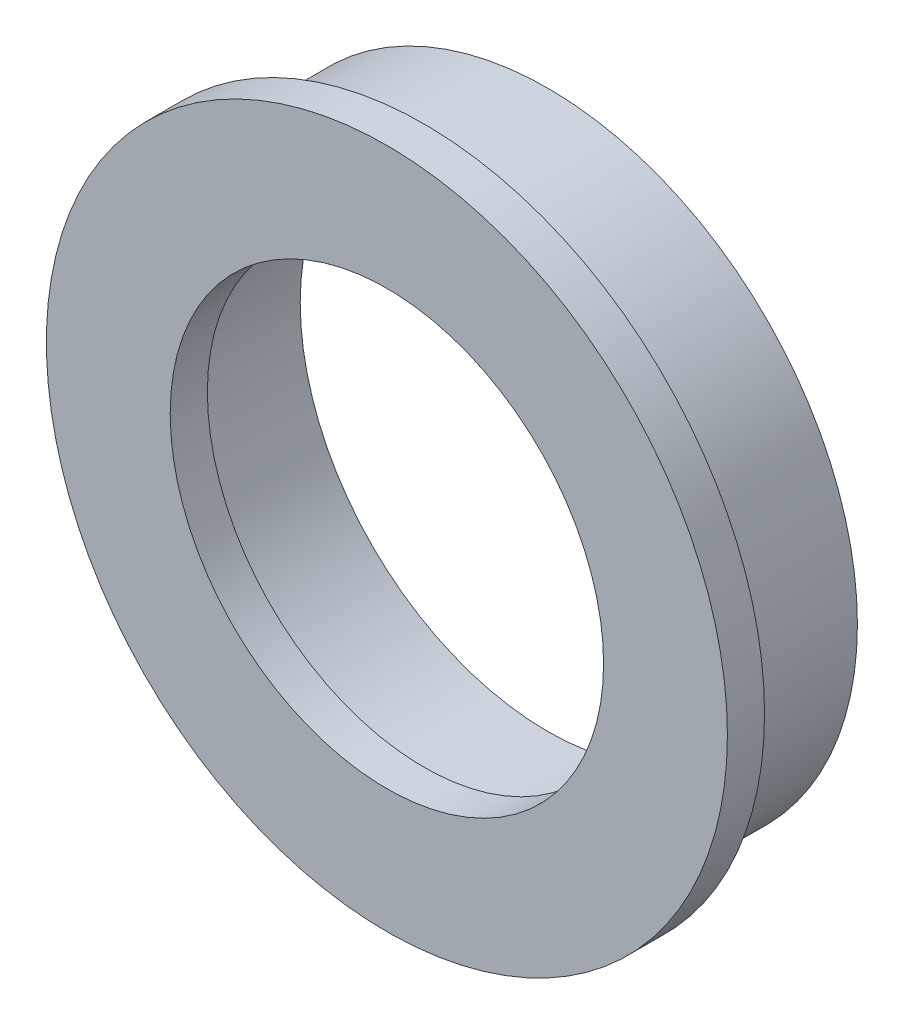
SolidWorks part; units mm, degrees
ref_plane "Спереди" through (0, 0, 0) normal (0, 0, 1) x (1, 0, 0)
ref_plane "Сверху" through (0, 0, 0) normal (0, 1, 0) x (1, 0, 0)
ref_plane "Справа" through (0, 0, 0) normal (1, 0, 0) x (0, 0, -1)
sketch "Эскиз1" plane through (0, 0, 0) normal (0, 0, 1) x (1, 0, 0)
  circle A0 centre (0, 0) radius 25
  dimension "D1" = 50
extrude "Бобышка-Вытянуть2" add sketch "Эскиз1" along normal blind 10
sketch "Эскиз2" plane through (0, 0, 0) normal (0, 0, 1) x (1, 0, 0)
  circle A0 centre (0, 0) radius 27.5
  dimension "D1" = 55
extrude "Бобышка-Вытянуть3" add sketch "Эскиз2" along normal blind 3 from offset 10
sketch "Эскиз3" plane through (0, 0, 0) normal (0, 0, 1) x (1, 0, 0)
  circle A0 centre (0, 0) radius 20
  dimension "D1" = 40
extrude "Вырез-Вытянуть1" cut sketch "Эскиз3" along normal blind 10
sketch "Эскиз4" plane through (0, 0, 0) normal (0, 0, 1) x (1, 0, 0)
  circle A0 centre (0, 0) radius 17.5
  dimension "D1" = 35
extrude "Вырез-Вытянуть2" cut sketch "Эскиз4" along normal blind 13
sketch "Эскиз5" plane through (0, 0, 10) normal (0, 0, -1) x (-1, 0, 0)
  line L2 (0, 0) -> (27.5, 0)
  line L3 (0, 0) -> (27.3954, -2.3968)
  line L4 (0, 0) -> (27.0822, -4.7753)
  line L5 (0, 0) -> (26.563, -7.1175)
  line L6 (0, 0) -> (25.8415, -9.4056)
  line L7 (0, 0) -> (24.9235, -11.622)
  line L8 (0, 0) -> (23.8157, -13.75)
  line L9 (0, 0) -> (22.5267, -15.7734)
  line L10 (0, 0) -> (21.0662, -17.6767)
  line L11 (0, 0) -> (19.4454, -19.4454)
  line L12 (0, 0) -> (17.6767, -21.0662)
  line L13 (0, 0) -> (15.7734, -22.5267)
  line L14 (0, 0) -> (13.75, -23.8157)
  line L15 (0, 0) -> (11.622, -24.9235)
  line L16 (0, 0) -> (9.4056, -25.8415)
  line L17 (0, 0) -> (7.1175, -26.563)
  line L18 (0, 0) -> (4.7753, -27.0822)
  line L19 (0, 0) -> (2.3968, -27.3954)
  line L20 (0, 0) -> (0, -27.5)
  line L21 (0, 0) -> (-2.3968, -27.3954)
  line L22 (0, 0) -> (-4.7753, -27.0822)
  line L23 (0, 0) -> (-7.1175, -26.563)
  line L24 (0, 0) -> (-9.4056, -25.8415)
  line L25 (0, 0) -> (-11.622, -24.9235)
  line L26 (0, 0) -> (-13.75, -23.8157)
  line L27 (0, 0) -> (-15.7734, -22.5267)
  line L28 (0, 0) -> (-17.6767, -21.0662)
  line L29 (0, 0) -> (-19.4454, -19.4454)
  line L30 (0, 0) -> (-21.0662, -17.6767)
  line L31 (0, 0) -> (-22.5267, -15.7734)
  line L32 (0, 0) -> (-23.8157, -13.75)
  line L33 (0, 0) -> (-24.9235, -11.622)
  line L34 (0, 0) -> (-25.8415, -9.4056)
  line L35 (0, 0) -> (-26.563, -7.1175)
  line L36 (0, 0) -> (-27.0822, -4.7753)
  line L37 (0, 0) -> (-27.3954, -2.3968)
  line L38 (0, 0) -> (-27.5, 0)
  line L39 (0, 0) -> (-27.3954, 2.3968)
  line L40 (0, 0) -> (-27.0822, 4.7753)
  line L41 (0, 0) -> (-26.563, 7.1175)
  line L42 (0, 0) -> (-25.8415, 9.4056)
  line L43 (0, 0) -> (-24.9235, 11.622)
  line L44 (0, 0) -> (-23.8157, 13.75)
  line L45 (0, 0) -> (-22.5267, 15.7734)
  line L46 (0, 0) -> (-21.0662, 17.6767)
  line L47 (0, 0) -> (-19.4454, 19.4454)
  line L48 (0, 0) -> (-17.6767, 21.0662)
  line L49 (0, 0) -> (-15.7734, 22.5267)
  line L50 (0, 0) -> (-13.75, 23.8157)
  line L51 (0, 0) -> (-11.622, 24.9235)
  line L52 (0, 0) -> (-9.4056, 25.8415)
  line L53 (0, 0) -> (-7.1175, 26.563)
  line L54 (0, 0) -> (-4.7753, 27.0822)
  line L55 (0, 0) -> (-2.3968, 27.3954)
  line L56 (0, 0) -> (0, 27.5)
  line L57 (0, 0) -> (2.3968, 27.3954)
  line L58 (0, 0) -> (4.7753, 27.0822)
  line L59 (0, 0) -> (7.1175, 26.563)
  line L60 (0, 0) -> (9.4056, 25.8415)
  line L61 (0, 0) -> (11.622, 24.9235)
  line L62 (0, 0) -> (13.75, 23.8157)
  line L63 (0, 0) -> (15.7734, 22.5267)
  line L64 (0, 0) -> (17.6767, 21.0662)
  line L65 (0, 0) -> (19.4454, 19.4454)
  line L66 (0, 0) -> (21.0662, 17.6767)
  line L67 (0, 0) -> (22.5267, 15.7734)
  line L68 (0, 0) -> (23.8157, 13.75)
  line L69 (0, 0) -> (24.9235, 11.622)
  line L70 (0, 0) -> (25.8415, 9.4056)
  line L71 (0, 0) -> (26.563, 7.1175)
  line L72 (0, 0) -> (27.0822, 4.7753)
  line L73 (0, 0) -> (27.3954, 2.3968)
  circle A1 centre (0, 0) radius 27.5 construction
  circle A2 centre (0, 0) radius 27.5
  circle A3 centre (0, 0) radius 17.5
  point P7 (0, 0)
  point P80 (0, 0)
  dimension "D1" = 72
  dimension "D2" = 35
  dimension "D3" = 55
sketch "Эскиз6" plane through (0, 0, 13) normal (0, 0, 1) x (1, 0, 0)
  line L0 (0, 0) -> (-27.5, 0)
  line L1 (0, 0) -> (-27.3954, 2.3968)
  line L2 (0, 0) -> (-27.0822, 4.7753)
  line L3 (0, 0) -> (-26.563, 7.1175)
  line L4 (0, 0) -> (-25.8415, 9.4056)
  line L5 (0, 0) -> (-24.9235, 11.622)
  line L6 (0, 0) -> (-23.8157, 13.75)
  line L7 (0, 0) -> (-22.5267, 15.7734)
  line L8 (0, 0) -> (-21.0662, 17.6767)
  line L9 (0, 0) -> (-19.4454, 19.4454)
  line L10 (0, 0) -> (-17.6767, 21.0662)
  line L11 (0, 0) -> (-15.7734, 22.5267)
  line L12 (0, 0) -> (-13.75, 23.8157)
  line L13 (0, 0) -> (-11.622, 24.9235)
  line L14 (0, 0) -> (-9.4056, 25.8415)
  line L15 (0, 0) -> (-7.1175, 26.563)
  line L16 (0, 0) -> (-4.7753, 27.0822)
  line L17 (0, 0) -> (-2.3968, 27.3954)
  line L18 (0, 0) -> (0, 27.5)
  line L19 (0, 0) -> (2.3968, 27.3954)
  line L20 (0, 0) -> (4.7753, 27.0822)
  line L21 (0, 0) -> (7.1175, 26.563)
  line L22 (0, 0) -> (9.4056, 25.8415)
  line L23 (0, 0) -> (11.622, 24.9235)
  line L24 (0, 0) -> (13.75, 23.8157)
  line L25 (0, 0) -> (15.7734, 22.5267)
  line L26 (0, 0) -> (17.6767, 21.0662)
  line L27 (0, 0) -> (19.4454, 19.4454)
  line L28 (0, 0) -> (21.0662, 17.6767)
  line L29 (0, 0) -> (22.5267, 15.7734)
  line L30 (0, 0) -> (23.8157, 13.75)
  line L31 (0, 0) -> (24.9235, 11.622)
  line L32 (0, 0) -> (25.8415, 9.4056)
  line L33 (0, 0) -> (26.563, 7.1175)
  line L34 (0, 0) -> (27.0822, 4.7753)
  line L35 (0, 0) -> (27.3954, 2.3968)
  line L36 (0, 0) -> (27.5, 0)
  line L37 (0, 0) -> (27.3954, -2.3968)
  line L38 (0, 0) -> (27.0822, -4.7753)
  line L39 (0, 0) -> (26.563, -7.1175)
  line L40 (0, 0) -> (25.8415, -9.4056)
  line L41 (0, 0) -> (24.9235, -11.622)
  line L42 (0, 0) -> (23.8157, -13.75)
  line L43 (0, 0) -> (22.5267, -15.7734)
  line L44 (0, 0) -> (21.0662, -17.6767)
  line L45 (0, 0) -> (19.4454, -19.4454)
  line L46 (0, 0) -> (17.6767, -21.0662)
  line L47 (0, 0) -> (15.7734, -22.5267)
  line L48 (0, 0) -> (13.75, -23.8157)
  line L49 (0, 0) -> (11.622, -24.9235)
  line L50 (0, 0) -> (9.4056, -25.8415)
  line L51 (0, 0) -> (7.1175, -26.563)
  line L52 (0, 0) -> (4.7753, -27.0822)
  line L53 (0, 0) -> (2.3968, -27.3954)
  line L54 (0, 0) -> (0, -27.5)
  line L55 (0, 0) -> (-2.3968, -27.3954)
  line L56 (0, 0) -> (-4.7753, -27.0822)
  line L57 (0, 0) -> (-7.1175, -26.563)
  line L58 (0, 0) -> (-9.4056, -25.8415)
  line L59 (0, 0) -> (-11.622, -24.9235)
  line L60 (0, 0) -> (-13.75, -23.8157)
  line L61 (0, 0) -> (-15.7734, -22.5267)
  line L62 (0, 0) -> (-17.6767, -21.0662)
  line L63 (0, 0) -> (-19.4454, -19.4454)
  line L64 (0, 0) -> (-21.0662, -17.6767)
  line L65 (0, 0) -> (-22.5267, -15.7734)
  line L66 (0, 0) -> (-23.8157, -13.75)
  line L67 (0, 0) -> (-24.9235, -11.622)
  line L68 (0, 0) -> (-25.8415, -9.4056)
  line L69 (0, 0) -> (-26.563, -7.1175)
  line L70 (0, 0) -> (-27.0822, -4.7753)
  line L71 (0, 0) -> (-27.3954, -2.3968)
  circle A0 centre (0, 0) radius 27.5
  circle A1 centre (0, 0) radius 17.5
  point P78 (0, 0)
  dimension "D2" = 35
  dimension "D3" = 55
  dimension "D1" = 72
sketch3d "Трехмерный эскиз2"
  line L4 (27.3954, 2.3968, 13) -> (17.4334, 1.5252, 13)
  line L5 (17.4334, 1.5252, 13) -> (17.5, 0, 10)
  line L6 (27.5, 0, 10) -> (17.5, 0, 10)
  line L7 (27.3954, 2.3968, 13) -> (27.5, 0, 10)
  line L8 (0, 0, 13) -> (0, 0, -49987) construction
  circle A0 centre (0, 0, 13) radius 17.5 construction
  circle A1 centre (0, 0, 10) radius 17.5 construction
  point P11 (0, 0, 30.5)
  point P15 (0, 0, -7.5)
sketch3d "Трехмерный эскиз3"
  line L0 (27.5, 0, 13) -> (17.5, 0, 13)
  line L1 (0, 0, 13) -> (27.5, 0, 13) construction
  line L2 (17.5, 0, 13) -> (17.4334, -1.5252, 10)
  line L3 (0, 0, 10) -> (27.3954, -2.3968, 10) construction
  line L4 (17.4334, -1.5252, 10) -> (27.3954, -2.3968, 10)
  line L5 (27.3954, -2.3968, 10) -> (27.5, 0, 13)
  line L6 (27.3954, -2.3968, 13) -> (27.0822, -4.7753, 10)
  line L7 (27.0822, -4.7753, 10) -> (17.2341, -3.0388, 10)
  line L8 (0, 0, 10) -> (27.0822, -4.7753, 10) construction
  line L9 (17.2341, -3.0388, 10) -> (17.4334, -1.5252, 13)
  line L10 (0, 0, 13) -> (27.3954, -2.3968, 13) construction
  line L11 (27.3954, -2.3968, 13) -> (17.4334, -1.5252, 13)
  line L12 (26.563, -7.1175, 10) -> (27.0822, -4.7753, 13)
  line L13 (27.0822, -4.7753, 13) -> (17.2341, -3.0388, 13)
  line L14 (0, 0, 13) -> (27.0822, -4.7753, 13) construction
  line L15 (17.2341, -3.0388, 13) -> (16.9037, -4.5293, 10)
  line L16 (0, 0, 10) -> (26.563, -7.1175, 10) construction
  line L17 (16.9037, -4.5293, 10) -> (26.563, -7.1175, 10)
  line L18 (26.563, -7.1175, 13) -> (25.8415, -9.4056, 10)
  line L19 (25.8415, -9.4056, 10) -> (16.4446, -5.9854, 10)
  line L20 (0, 0, 10) -> (25.8415, -9.4056, 10) construction
  line L21 (16.4446, -5.9854, 10) -> (16.9037, -4.5293, 13)
  line L22 (0, 0, 13) -> (26.563, -7.1175, 13) construction
  line L23 (16.9037, -4.5293, 13) -> (26.563, -7.1175, 13)
  line L24 (24.9235, -11.622, 10) -> (25.8415, -9.4056, 13)
  line L25 (25.8415, -9.4056, 13) -> (16.4446, -5.9854, 13)
  line L26 (0, 0, 13) -> (25.8415, -9.4056, 13) construction
  line L27 (16.4446, -5.9854, 13) -> (15.8604, -7.3958, 10)
  line L28 (0, 0, 10) -> (24.9235, -11.622, 10) construction
  line L29 (15.8604, -7.3958, 10) -> (24.9235, -11.622, 10)
  line L30 (23.8157, -13.75, 10) -> (24.9235, -11.622, 13)
  line L31 (24.9235, -11.622, 13) -> (15.8604, -7.3958, 13)
  line L32 (0, 0, 13) -> (24.9235, -11.622, 13) construction
  line L33 (15.8604, -7.3958, 13) -> (15.1554, -8.75, 10)
  line L34 (0, 0, 10) -> (23.8157, -13.75, 10) construction
  line L35 (15.1554, -8.75, 10) -> (23.8157, -13.75, 10)
  line L36 (22.5267, -15.7734, 10) -> (23.8157, -13.75, 13)
  line L37 (23.8157, -13.75, 13) -> (15.1554, -8.75, 13)
  line L38 (0, 0, 13) -> (23.8157, -13.75, 13) construction
  line L39 (15.1554, -8.75, 13) -> (14.3352, -10.0376, 10)
  line L40 (0, 0, 10) -> (22.5267, -15.7734, 10) construction
  line L41 (14.3352, -10.0376, 10) -> (22.5267, -15.7734, 10)
  line L42 (22.5267, -15.7734, 13) -> (14.3352, -10.0376, 13)
  line L43 (0, 0, 13) -> (22.5267, -15.7734, 13) construction
  line L44 (22.5267, -15.7734, 13) -> (21.0662, -17.6767, 10)
  line L45 (21.0662, -17.6767, 10) -> (13.4058, -11.2488, 10)
  line L46 (0, 0, 10) -> (21.0662, -17.6767, 10) construction
  line L47 (13.4058, -11.2488, 10) -> (14.3352, -10.0376, 13)
  line L48 (21.0662, -17.6767, 13) -> (19.4454, -19.4454, 10)
  line L49 (21.0662, -17.6767, 13) -> (13.4058, -11.2488, 13)
  line L50 (0, 0, 13) -> (21.0662, -17.6767, 13) construction
  line L51 (13.4058, -11.2488, 13) -> (12.3744, -12.3744, 10)
  line L52 (0, 0, 10) -> (19.4454, -19.4454, 10) construction
  line L53 (12.3744, -12.3744, 10) -> (19.4454, -19.4454, 10)
  line L54 (19.4454, -19.4454, 13) -> (17.6767, -21.0662, 10)
  line L55 (17.6767, -21.0662, 10) -> (11.2488, -13.4058, 10)
  line L56 (0, 0, 10) -> (17.6767, -21.0662, 10) construction
  line L57 (11.2488, -13.4058, 10) -> (12.3744, -12.3744, 13)
  line L58 (0, 0, 13) -> (19.4454, -19.4454, 13) construction
  line L59 (12.3744, -12.3744, 13) -> (19.4454, -19.4454, 13)
  line L60 (17.6767, -21.0662, 13) -> (15.7734, -22.5267, 10)
  line L61 (15.7734, -22.5267, 10) -> (10.0376, -14.3352, 10)
  line L62 (0, 0, 10) -> (15.7734, -22.5267, 10) construction
  line L63 (10.0376, -14.3352, 10) -> (11.2488, -13.4058, 13)
  line L64 (0, 0, 13) -> (17.6767, -21.0662, 13) construction
  line L65 (11.2488, -13.4058, 13) -> (17.6767, -21.0662, 13)
  line L66 (13.75, -23.8157, 10) -> (15.7734, -22.5267, 13)
  line L67 (15.7734, -22.5267, 13) -> (10.0376, -14.3352, 13)
  line L68 (0, 0, 13) -> (15.7734, -22.5267, 13) construction
  line L69 (10.0376, -14.3352, 13) -> (8.75, -15.1554, 10)
  line L70 (0, 0, 10) -> (13.75, -23.8157, 10) construction
  line L71 (8.75, -15.1554, 10) -> (13.75, -23.8157, 10)
  line L72 (11.622, -24.9235, 10) -> (13.75, -23.8157, 13)
  line L73 (13.75, -23.8157, 13) -> (8.75, -15.1554, 13)
  line L74 (0, 0, 13) -> (13.75, -23.8157, 13) construction
  line L75 (8.75, -15.1554, 13) -> (7.3958, -15.8604, 10)
  line L76 (0, 0, 10) -> (11.622, -24.9235, 10) construction
  line L77 (7.3958, -15.8604, 10) -> (11.622, -24.9235, 10)
  line L78 (9.4056, -25.8415, 10) -> (11.622, -24.9235, 13)
  line L79 (11.622, -24.9235, 13) -> (7.3958, -15.8604, 13)
  line L80 (0, 0, 13) -> (11.622, -24.9235, 13) construction
  line L81 (7.3958, -15.8604, 13) -> (5.9854, -16.4446, 10)
  line L82 (0, 0, 10) -> (9.4056, -25.8415, 10) construction
  line L83 (5.9854, -16.4446, 10) -> (9.4056, -25.8415, 10)
  line L84 (7.1175, -26.563, 10) -> (9.4056, -25.8415, 13)
  line L85 (9.4056, -25.8415, 13) -> (5.9854, -16.4446, 13)
  line L86 (0, 0, 13) -> (9.4056, -25.8415, 13) construction
  line L87 (5.9854, -16.4446, 13) -> (4.5293, -16.9037, 10)
  line L88 (0, 0, 10) -> (7.1175, -26.563, 10) construction
  line L89 (4.5293, -16.9037, 10) -> (7.1175, -26.563, 10)
  line L90 (4.7753, -27.0822, 10) -> (7.1175, -26.563, 13)
  line L91 (7.1175, -26.563, 13) -> (4.5293, -16.9037, 13)
  line L92 (0, 0, 13) -> (7.1175, -26.563, 13) construction
  line L93 (4.5293, -16.9037, 13) -> (3.0388, -17.2341, 10)
  line L94 (0, 0, 10) -> (4.7753, -27.0822, 10) construction
  line L95 (3.0388, -17.2341, 10) -> (4.7753, -27.0822, 10)
  line L96 (2.3968, -27.3954, 10) -> (4.7753, -27.0822, 13)
  line L97 (4.7753, -27.0822, 13) -> (3.0388, -17.2341, 13)
  line L98 (0, 0, 13) -> (4.7753, -27.0822, 13) construction
  line L99 (3.0388, -17.2341, 13) -> (1.5252, -17.4334, 10)
  line L100 (0, 0, 10) -> (2.3968, -27.3954, 10) construction
  line L101 (1.5252, -17.4334, 10) -> (2.3968, -27.3954, 10)
  line L102 (2.3968, -27.3954, 13) -> (1.5252, -17.4334, 13)
  line L103 (0, 0, 13) -> (2.3968, -27.3954, 13) construction
  line L104 (1.5252, -17.4334, 13) -> (0, -17.5, 10)
  line L105 (0, 0, 10) -> (0, -27.5, 10) construction
  line L106 (0, -17.5, 10) -> (0, -27.5, 10)
  line L107 (0, -27.5, 10) -> (2.3968, -27.3954, 13)
  line L108 (-2.3968, -27.3954, 10) -> (0, -27.5, 13)
  line L109 (0, -27.5, 13) -> (0, -17.5, 13)
  line L110 (0, 0, 13) -> (0, -27.5, 13) construction
  line L111 (0, -17.5, 13) -> (-1.5252, -17.4334, 10)
  line L112 (0, 0, 10) -> (-2.3968, -27.3954, 10) construction
  line L113 (-1.5252, -17.4334, 10) -> (-2.3968, -27.3954, 10)
  line L114 (-4.7753, -27.0822, 10) -> (-2.3968, -27.3954, 13)
  line L115 (-2.3968, -27.3954, 13) -> (-1.5252, -17.4334, 13)
  line L116 (0, 0, 13) -> (-2.3968, -27.3954, 13) construction
  line L117 (-1.5252, -17.4334, 13) -> (-3.0388, -17.2341, 10)
  line L118 (0, 0, 10) -> (-4.7753, -27.0822, 10) construction
  line L119 (-3.0388, -17.2341, 10) -> (-4.7753, -27.0822, 10)
  line L120 (-7.1175, -26.563, 10) -> (-4.7753, -27.0822, 13)
  line L121 (-4.7753, -27.0822, 13) -> (-3.0388, -17.2341, 13)
  line L122 (0, 0, 13) -> (-4.7753, -27.0822, 13) construction
  line L123 (-3.0388, -17.2341, 13) -> (-4.5293, -16.9037, 10)
  line L124 (0, 0, 10) -> (-7.1175, -26.563, 10) construction
  line L125 (-4.5293, -16.9037, 10) -> (-7.1175, -26.563, 10)
  line L126 (-9.4056, -25.8415, 10) -> (-7.1175, -26.563, 13)
  line L127 (-7.1175, -26.563, 13) -> (-4.5293, -16.9037, 13)
  line L128 (0, 0, 13) -> (-7.1175, -26.563, 13) construction
  line L129 (-4.5293, -16.9037, 13) -> (-5.9854, -16.4446, 10)
  line L130 (0, 0, 10) -> (-9.4056, -25.8415, 10) construction
  line L131 (-5.9854, -16.4446, 10) -> (-9.4056, -25.8415, 10)
  line L132 (-11.622, -24.9235, 10) -> (-9.4056, -25.8415, 13)
  line L133 (-9.4056, -25.8415, 13) -> (-5.9854, -16.4446, 13)
  line L134 (0, 0, 13) -> (-9.4056, -25.8415, 13) construction
  line L135 (-5.9854, -16.4446, 13) -> (-7.3958, -15.8604, 10)
  line L136 (0, 0, 10) -> (-11.622, -24.9235, 10) construction
  line L137 (-7.3958, -15.8604, 10) -> (-11.622, -24.9235, 10)
  line L138 (-13.75, -23.8157, 10) -> (-11.622, -24.9235, 13)
  line L139 (-11.622, -24.9235, 13) -> (-7.3958, -15.8604, 13)
  line L140 (0, 0, 13) -> (-11.622, -24.9235, 13) construction
  line L141 (-7.3958, -15.8604, 13) -> (-8.75, -15.1554, 10)
  line L142 (0, 0, 10) -> (-13.75, -23.8157, 10) construction
  line L143 (-8.75, -15.1554, 10) -> (-13.75, -23.8157, 10)
  line L144 (-15.7734, -22.5267, 10) -> (-13.75, -23.8157, 13)
  line L145 (-13.75, -23.8157, 13) -> (-8.75, -15.1554, 13)
  line L146 (0, 0, 13) -> (-13.75, -23.8157, 13) construction
  line L147 (-8.75, -15.1554, 13) -> (-10.0376, -14.3352, 10)
  line L148 (0, 0, 10) -> (-15.7734, -22.5267, 10) construction
  line L149 (-10.0376, -14.3352, 10) -> (-15.7734, -22.5267, 10)
  line L150 (-17.6767, -21.0662, 10) -> (-15.7734, -22.5267, 13)
  line L151 (-15.7734, -22.5267, 13) -> (-10.0376, -14.3352, 13)
  line L152 (0, 0, 13) -> (-15.7734, -22.5267, 13) construction
  line L153 (-10.0376, -14.3352, 13) -> (-11.2488, -13.4058, 10)
  line L154 (0, 0, 10) -> (-17.6767, -21.0662, 10) construction
  line L155 (-11.2488, -13.4058, 10) -> (-17.6767, -21.0662, 10)
  line L156 (-19.4454, -19.4454, 10) -> (-17.6767, -21.0662, 13)
  line L157 (-17.6767, -21.0662, 13) -> (-11.2488, -13.4058, 13)
  line L158 (0, 0, 13) -> (-17.6767, -21.0662, 13) construction
  line L159 (-11.2488, -13.4058, 13) -> (-12.3744, -12.3744, 10)
  line L160 (0, 0, 10) -> (-19.4454, -19.4454, 10) construction
  line L161 (-12.3744, -12.3744, 10) -> (-19.4454, -19.4454, 10)
  line L162 (-21.0662, -17.6767, 10) -> (-19.4454, -19.4454, 13)
  line L163 (-19.4454, -19.4454, 13) -> (-12.3744, -12.3744, 13)
  line L164 (0, 0, 13) -> (-19.4454, -19.4454, 13) construction
  line L165 (-12.3744, -12.3744, 13) -> (-13.4058, -11.2488, 10)
  line L166 (0, 0, 10) -> (-21.0662, -17.6767, 10) construction
  line L167 (-13.4058, -11.2488, 10) -> (-21.0662, -17.6767, 10)
  line L168 (-22.5267, -15.7734, 10) -> (-21.0662, -17.6767, 13)
  line L169 (-21.0662, -17.6767, 13) -> (-13.4058, -11.2488, 13)
  line L170 (0, 0, 13) -> (-21.0662, -17.6767, 13) construction
  line L171 (-13.4058, -11.2488, 13) -> (-14.3352, -10.0376, 10)
  line L172 (0, 0, 10) -> (-22.5267, -15.7734, 10) construction
  line L173 (-14.3352, -10.0376, 10) -> (-22.5267, -15.7734, 10)
  line L174 (-23.8157, -13.75, 10) -> (-22.5267, -15.7734, 13)
  line L175 (-22.5267, -15.7734, 13) -> (-14.3352, -10.0376, 13)
  line L176 (0, 0, 13) -> (-22.5267, -15.7734, 13) construction
  line L177 (-14.3352, -10.0376, 13) -> (-15.1554, -8.75, 10)
  line L178 (0, 0, 10) -> (-23.8157, -13.75, 10) construction
  line L179 (-15.1554, -8.75, 10) -> (-23.8157, -13.75, 10)
  line L180 (-24.9235, -11.622, 10) -> (-23.8157, -13.75, 13)
  line L181 (-23.8157, -13.75, 13) -> (-15.1554, -8.75, 13)
  line L182 (0, 0, 13) -> (-23.8157, -13.75, 13) construction
  line L183 (-15.1554, -8.75, 13) -> (-15.8604, -7.3958, 10)
  line L184 (0, 0, 10) -> (-24.9235, -11.622, 10) construction
  line L185 (-15.8604, -7.3958, 10) -> (-24.9235, -11.622, 10)
  line L186 (-25.8415, -9.4056, 10) -> (-24.9235, -11.622, 13)
  line L187 (-24.9235, -11.622, 13) -> (-15.8604, -7.3958, 13)
  line L188 (0, 0, 13) -> (-24.9235, -11.622, 13) construction
  line L189 (-15.8604, -7.3958, 13) -> (-16.4446, -5.9854, 10)
  line L190 (0, 0, 10) -> (-25.8415, -9.4056, 10) construction
  line L191 (-16.4446, -5.9854, 10) -> (-25.8415, -9.4056, 10)
  line L192 (-26.563, -7.1175, 10) -> (-25.8415, -9.4056, 13)
  line L193 (-25.8415, -9.4056, 13) -> (-16.4446, -5.9854, 13)
  line L194 (0, 0, 13) -> (-25.8415, -9.4056, 13) construction
  line L195 (-16.4446, -5.9854, 13) -> (-16.9037, -4.5293, 10)
  line L196 (0, 0, 10) -> (-26.563, -7.1175, 10) construction
  line L197 (-16.9037, -4.5293, 10) -> (-26.563, -7.1175, 10)
  line L198 (-27.0822, -4.7753, 10) -> (-26.563, -7.1175, 13)
  line L199 (-26.563, -7.1175, 13) -> (-16.9037, -4.5293, 13)
  line L200 (0, 0, 13) -> (-26.563, -7.1175, 13) construction
  line L201 (-16.9037, -4.5293, 13) -> (-17.2341, -3.0388, 10)
  line L202 (0, 0, 10) -> (-27.0822, -4.7753, 10) construction
  line L203 (-17.2341, -3.0388, 10) -> (-27.0822, -4.7753, 10)
  line L204 (-27.3954, -2.3968, 10) -> (-27.0822, -4.7753, 13)
  line L205 (-27.0822, -4.7753, 13) -> (-17.2341, -3.0388, 13)
  line L206 (0, 0, 13) -> (-27.0822, -4.7753, 13) construction
  line L207 (-17.2341, -3.0388, 13) -> (-17.4334, -1.5252, 10)
  line L208 (0, 0, 10) -> (-27.3954, -2.3968, 10) construction
  line L209 (-17.4334, -1.5252, 10) -> (-27.3954, -2.3968, 10)
  line L210 (-27.5, 0, 10) -> (-27.3954, -2.3968, 13)
  line L211 (-27.3954, -2.3968, 13) -> (-17.4334, -1.5252, 13)
  line L212 (0, 0, 13) -> (-27.3954, -2.3968, 13) construction
  line L213 (-17.4334, -1.5252, 13) -> (-17.5, 0, 10)
  line L214 (0, 0, 10) -> (-27.5, 0, 10) construction
  line L215 (-17.5, 0, 10) -> (-27.5, 0, 10)
  line L216 (-27.3954, 2.3968, 10) -> (-27.5, 0, 13)
  line L217 (-27.5, 0, 13) -> (-17.5, 0, 13)
  line L218 (0, 0, 13) -> (-27.5, 0, 13) construction
  line L219 (-17.5, 0, 13) -> (-17.4334, 1.5252, 10)
  line L220 (0, 0, 10) -> (-27.3954, 2.3968, 10) construction
  line L221 (-17.4334, 1.5252, 10) -> (-27.3954, 2.3968, 10)
  line L222 (-27.0822, 4.7753, 10) -> (-27.3954, 2.3968, 13)
  line L223 (-27.3954, 2.3968, 13) -> (-17.4334, 1.5252, 13)
  line L224 (0, 0, 13) -> (-27.3954, 2.3968, 13) construction
  line L225 (-17.4334, 1.5252, 13) -> (-17.2341, 3.0388, 10)
  line L226 (0, 0, 10) -> (-27.0822, 4.7753, 10) construction
  line L227 (-17.2341, 3.0388, 10) -> (-27.0822, 4.7753, 10)
  line L228 (-26.563, 7.1175, 10) -> (-27.0822, 4.7753, 13)
  line L229 (-27.0822, 4.7753, 13) -> (-17.2341, 3.0388, 13)
  line L230 (0, 0, 13) -> (-27.0822, 4.7753, 13) construction
  line L231 (-17.2341, 3.0388, 13) -> (-16.9037, 4.5293, 10)
  line L232 (0, 0, 10) -> (-26.563, 7.1175, 10) construction
  line L233 (-16.9037, 4.5293, 10) -> (-26.563, 7.1175, 10)
  line L234 (-25.8415, 9.4056, 10) -> (-26.563, 7.1175, 13)
  line L235 (-26.563, 7.1175, 13) -> (-16.9037, 4.5293, 13)
  line L236 (0, 0, 13) -> (-26.563, 7.1175, 13) construction
  line L237 (-16.9037, 4.5293, 13) -> (-16.4446, 5.9854, 10)
  line L238 (0, 0, 10) -> (-25.8415, 9.4056, 10) construction
  line L239 (-16.4446, 5.9854, 10) -> (-25.8415, 9.4056, 10)
  line L240 (-24.9235, 11.622, 10) -> (-25.8415, 9.4056, 13)
  line L241 (-25.8415, 9.4056, 13) -> (-16.4446, 5.9854, 13)
  line L242 (0, 0, 13) -> (-25.8415, 9.4056, 13) construction
  line L243 (-16.4446, 5.9854, 13) -> (-15.8604, 7.3958, 10)
  line L244 (0, 0, 10) -> (-24.9235, 11.622, 10) construction
  line L245 (-15.8604, 7.3958, 10) -> (-24.9235, 11.622, 10)
  line L246 (-23.8157, 13.75, 10) -> (-24.9235, 11.622, 13)
  line L247 (-24.9235, 11.622, 13) -> (-15.8604, 7.3958, 13)
  line L248 (0, 0, 13) -> (-24.9235, 11.622, 13) construction
  line L249 (-15.8604, 7.3958, 13) -> (-15.1554, 8.75, 10)
  line L250 (0, 0, 10) -> (-23.8157, 13.75, 10) construction
  line L251 (-15.1554, 8.75, 10) -> (-23.8157, 13.75, 10)
  line L252 (-22.5267, 15.7734, 10) -> (-23.8157, 13.75, 13)
  line L253 (-23.8157, 13.75, 13) -> (-15.1554, 8.75, 13)
  line L254 (0, 0, 13) -> (-23.8157, 13.75, 13) construction
  line L255 (-15.1554, 8.75, 13) -> (-14.3352, 10.0376, 10)
  line L256 (0, 0, 10) -> (-22.5267, 15.7734, 10) construction
  line L257 (-14.3352, 10.0376, 10) -> (-22.5267, 15.7734, 10)
  line L258 (-21.0662, 17.6767, 10) -> (-22.5267, 15.7734, 13)
  line L259 (-22.5267, 15.7734, 13) -> (-14.3352, 10.0376, 13)
  line L260 (0, 0, 13) -> (-22.5267, 15.7734, 13) construction
  line L261 (-14.3352, 10.0376, 13) -> (-13.4058, 11.2488, 10)
  line L262 (0, 0, 10) -> (-21.0662, 17.6767, 10) construction
  line L263 (-13.4058, 11.2488, 10) -> (-21.0662, 17.6767, 10)
  line L264 (-19.4454, 19.4454, 10) -> (-21.0662, 17.6767, 13)
  line L265 (-21.0662, 17.6767, 13) -> (-13.4058, 11.2488, 13)
  line L266 (0, 0, 13) -> (-21.0662, 17.6767, 13) construction
  line L267 (-13.4058, 11.2488, 13) -> (-12.3744, 12.3744, 10)
  line L268 (0, 0, 10) -> (-19.4454, 19.4454, 10) construction
  line L269 (-12.3744, 12.3744, 10) -> (-19.4454, 19.4454, 10)
  line L270 (-17.6767, 21.0662, 10) -> (-19.4454, 19.4454, 13)
  line L271 (-19.4454, 19.4454, 13) -> (-12.3744, 12.3744, 13)
  line L272 (0, 0, 13) -> (-19.4454, 19.4454, 13) construction
  line L273 (-12.3744, 12.3744, 13) -> (-11.2488, 13.4058, 10)
  line L274 (0, 0, 10) -> (-17.6767, 21.0662, 10) construction
  line L275 (-11.2488, 13.4058, 10) -> (-17.6767, 21.0662, 10)
  line L276 (-15.7734, 22.5267, 10) -> (-17.6767, 21.0662, 13)
  line L277 (-17.6767, 21.0662, 13) -> (-11.2488, 13.4058, 13)
  line L278 (0, 0, 13) -> (-17.6767, 21.0662, 13) construction
  line L279 (-11.2488, 13.4058, 13) -> (-10.0376, 14.3352, 10)
  line L280 (0, 0, 10) -> (-15.7734, 22.5267, 10) construction
  line L281 (-10.0376, 14.3352, 10) -> (-15.7734, 22.5267, 10)
  line L282 (-13.75, 23.8157, 10) -> (-15.7734, 22.5267, 13)
  line L283 (-15.7734, 22.5267, 13) -> (-10.0376, 14.3352, 13)
  line L284 (0, 0, 13) -> (-15.7734, 22.5267, 13) construction
  line L285 (-10.0376, 14.3352, 13) -> (-8.75, 15.1554, 10)
  line L286 (0, 0, 10) -> (-13.75, 23.8157, 10) construction
  line L287 (-8.75, 15.1554, 10) -> (-13.75, 23.8157, 10)
  line L288 (-11.622, 24.9235, 10) -> (-13.75, 23.8157, 13)
  line L289 (-13.75, 23.8157, 13) -> (-8.75, 15.1554, 13)
  line L290 (0, 0, 13) -> (-13.75, 23.8157, 13) construction
  line L291 (-8.75, 15.1554, 13) -> (-7.3958, 15.8604, 10)
  line L292 (0, 0, 10) -> (-11.622, 24.9235, 10) construction
  line L293 (-7.3958, 15.8604, 10) -> (-11.622, 24.9235, 10)
  line L294 (-9.4056, 25.8415, 10) -> (-11.622, 24.9235, 13)
  line L295 (-11.622, 24.9235, 13) -> (-7.3958, 15.8604, 13)
  line L296 (0, 0, 13) -> (-11.622, 24.9235, 13) construction
  line L297 (-7.3958, 15.8604, 13) -> (-5.9854, 16.4446, 10)
  line L298 (0, 0, 10) -> (-9.4056, 25.8415, 10) construction
  line L299 (-5.9854, 16.4446, 10) -> (-9.4056, 25.8415, 10)
  line L300 (-7.1175, 26.563, 10) -> (-9.4056, 25.8415, 13)
  line L301 (-9.4056, 25.8415, 13) -> (-5.9854, 16.4446, 13)
  line L302 (0, 0, 13) -> (-9.4056, 25.8415, 13) construction
  line L303 (-5.9854, 16.4446, 13) -> (-4.5293, 16.9037, 10)
  line L304 (0, 0, 10) -> (-7.1175, 26.563, 10) construction
  line L305 (-4.5293, 16.9037, 10) -> (-7.1175, 26.563, 10)
  line L306 (-4.7753, 27.0822, 10) -> (-7.1175, 26.563, 13)
  line L307 (-7.1175, 26.563, 13) -> (-4.5293, 16.9037, 13)
  line L308 (0, 0, 13) -> (-7.1175, 26.563, 13) construction
  line L309 (-4.5293, 16.9037, 13) -> (-3.0388, 17.2341, 10)
  line L310 (0, 0, 10) -> (-4.7753, 27.0822, 10) construction
  line L311 (-3.0388, 17.2341, 10) -> (-4.7753, 27.0822, 10)
  line L312 (-2.3968, 27.3954, 10) -> (-4.7753, 27.0822, 13)
  line L313 (-4.7753, 27.0822, 13) -> (-3.0388, 17.2341, 13)
  line L314 (0, 0, 13) -> (-4.7753, 27.0822, 13) construction
  line L315 (-3.0388, 17.2341, 13) -> (-1.5252, 17.4334, 10)
  line L316 (0, 0, 10) -> (-2.3968, 27.3954, 10) construction
  line L317 (-1.5252, 17.4334, 10) -> (-2.3968, 27.3954, 10)
  line L318 (0, 27.5, 10) -> (-2.3968, 27.3954, 13)
  line L319 (-2.3968, 27.3954, 13) -> (-1.5252, 17.4334, 13)
  line L320 (0, 0, 13) -> (-2.3968, 27.3954, 13) construction
  line L321 (-1.5252, 17.4334, 13) -> (0, 17.5, 10)
  line L322 (0, 0, 10) -> (0, 27.5, 10) construction
  line L323 (0, 17.5, 10) -> (0, 27.5, 10)
  line L324 (2.3968, 27.3954, 10) -> (0, 27.5, 13)
  line L325 (0, 27.5, 13) -> (0, 17.5, 13)
  line L326 (0, 0, 13) -> (0, 27.5, 13) construction
  line L327 (0, 17.5, 13) -> (1.5252, 17.4334, 10)
  line L328 (0, 0, 10) -> (2.3968, 27.3954, 10) construction
  line L329 (1.5252, 17.4334, 10) -> (2.3968, 27.3954, 10)
  line L330 (4.7753, 27.0822, 10) -> (2.3968, 27.3954, 13)
  line L331 (2.3968, 27.3954, 13) -> (1.5252, 17.4334, 13)
  line L332 (0, 0, 13) -> (2.3968, 27.3954, 13) construction
  line L333 (1.5252, 17.4334, 13) -> (3.0388, 17.2341, 10)
  line L334 (0, 0, 10) -> (4.7753, 27.0822, 10) construction
  line L335 (3.0388, 17.2341, 10) -> (4.7753, 27.0822, 10)
  line L336 (7.1175, 26.563, 10) -> (4.7753, 27.0822, 13)
  line L337 (4.7753, 27.0822, 13) -> (3.0388, 17.2341, 13)
  line L338 (0, 0, 13) -> (4.7753, 27.0822, 13) construction
  line L339 (3.0388, 17.2341, 13) -> (4.5293, 16.9037, 10)
  line L340 (0, 0, 10) -> (7.1175, 26.563, 10) construction
  line L341 (4.5293, 16.9037, 10) -> (7.1175, 26.563, 10)
  line L342 (9.4056, 25.8415, 10) -> (7.1175, 26.563, 13)
  line L343 (7.1175, 26.563, 13) -> (4.5293, 16.9037, 13)
  line L344 (0, 0, 13) -> (7.1175, 26.563, 13) construction
  line L345 (4.5293, 16.9037, 13) -> (5.9854, 16.4446, 10)
  line L346 (0, 0, 10) -> (9.4056, 25.8415, 10) construction
  line L347 (5.9854, 16.4446, 10) -> (9.4056, 25.8415, 10)
  line L348 (11.622, 24.9235, 10) -> (9.4056, 25.8415, 13)
  line L349 (9.4056, 25.8415, 13) -> (5.9854, 16.4446, 13)
  line L350 (0, 0, 13) -> (9.4056, 25.8415, 13) construction
  line L351 (5.9854, 16.4446, 13) -> (7.3958, 15.8604, 10)
  line L352 (0, 0, 10) -> (11.622, 24.9235, 10) construction
  line L353 (7.3958, 15.8604, 10) -> (11.622, 24.9235, 10)
  line L354 (13.75, 23.8157, 10) -> (11.622, 24.9235, 13)
  line L355 (11.622, 24.9235, 13) -> (7.3958, 15.8604, 13)
  line L356 (0, 0, 13) -> (11.622, 24.9235, 13) construction
  line L357 (7.3958, 15.8604, 13) -> (8.75, 15.1554, 10)
  line L358 (0, 0, 10) -> (13.75, 23.8157, 10) construction
  line L359 (8.75, 15.1554, 10) -> (13.75, 23.8157, 10)
  line L360 (15.7734, 22.5267, 10) -> (13.75, 23.8157, 13)
  line L361 (13.75, 23.8157, 13) -> (8.75, 15.1554, 13)
  line L362 (0, 0, 13) -> (13.75, 23.8157, 13) construction
  line L363 (8.75, 15.1554, 13) -> (10.0376, 14.3352, 10)
  line L364 (0, 0, 10) -> (15.7734, 22.5267, 10) construction
  line L365 (10.0376, 14.3352, 10) -> (15.7734, 22.5267, 10)
  line L366 (17.6767, 21.0662, 10) -> (15.7734, 22.5267, 13)
  line L367 (15.7734, 22.5267, 13) -> (10.0376, 14.3352, 13)
  line L368 (0, 0, 13) -> (15.7734, 22.5267, 13) construction
  line L369 (10.0376, 14.3352, 13) -> (11.2488, 13.4058, 10)
  line L370 (0, 0, 10) -> (17.6767, 21.0662, 10) construction
  line L371 (11.2488, 13.4058, 10) -> (17.6767, 21.0662, 10)
  line L372 (19.4454, 19.4454, 10) -> (17.6767, 21.0662, 13)
  line L373 (17.6767, 21.0662, 13) -> (11.2488, 13.4058, 13)
  line L374 (0, 0, 13) -> (17.6767, 21.0662, 13) construction
  line L375 (11.2488, 13.4058, 13) -> (12.3744, 12.3744, 10)
  line L376 (0, 0, 10) -> (19.4454, 19.4454, 10) construction
  line L377 (12.3744, 12.3744, 10) -> (19.4454, 19.4454, 10)
  line L378 (21.0662, 17.6767, 10) -> (19.4454, 19.4454, 13)
  line L379 (19.4454, 19.4454, 13) -> (12.3744, 12.3744, 13)
  line L380 (0, 0, 13) -> (19.4454, 19.4454, 13) construction
  line L381 (12.3744, 12.3744, 13) -> (13.4058, 11.2488, 10)
  line L382 (0, 0, 10) -> (21.0662, 17.6767, 10) construction
  line L383 (13.4058, 11.2488, 10) -> (21.0662, 17.6767, 10)
  line L384 (22.5267, 15.7734, 10) -> (21.0662, 17.6767, 13)
  line L385 (21.0662, 17.6767, 13) -> (13.4058, 11.2488, 13)
  line L386 (0, 0, 13) -> (21.0662, 17.6767, 13) construction
  line L387 (13.4058, 11.2488, 13) -> (14.3352, 10.0376, 10)
  line L388 (0, 0, 10) -> (22.5267, 15.7734, 10) construction
  line L389 (14.3352, 10.0376, 10) -> (22.5267, 15.7734, 10)
  line L390 (23.8157, 13.75, 10) -> (22.5267, 15.7734, 13)
  line L391 (22.5267, 15.7734, 13) -> (14.3352, 10.0376, 13)
  line L392 (0, 0, 13) -> (22.5267, 15.7734, 13) construction
  line L393 (14.3352, 10.0376, 13) -> (15.1554, 8.75, 10)
  line L394 (0, 0, 10) -> (23.8157, 13.75, 10) construction
  line L395 (15.1554, 8.75, 10) -> (23.8157, 13.75, 10)
  line L396 (24.9235, 11.622, 10) -> (23.8157, 13.75, 13)
  line L397 (23.8157, 13.75, 13) -> (15.1554, 8.75, 13)
  line L398 (0, 0, 13) -> (23.8157, 13.75, 13) construction
  line L399 (15.1554, 8.75, 13) -> (15.8604, 7.3958, 10)
  line L400 (0, 0, 10) -> (24.9235, 11.622, 10) construction
  line L401 (15.8604, 7.3958, 10) -> (24.9235, 11.622, 10)
  line L402 (25.8415, 9.4056, 10) -> (24.9235, 11.622, 13)
  line L403 (24.9235, 11.622, 13) -> (15.8604, 7.3958, 13)
  line L404 (0, 0, 13) -> (24.9235, 11.622, 13) construction
  line L405 (15.8604, 7.3958, 13) -> (16.4446, 5.9854, 10)
  line L406 (0, 0, 10) -> (25.8415, 9.4056, 10) construction
  line L407 (16.4446, 5.9854, 10) -> (25.8415, 9.4056, 10)
  line L408 (26.563, 7.1175, 10) -> (25.8415, 9.4056, 13)
  line L409 (25.8415, 9.4056, 13) -> (16.4446, 5.9854, 13)
  line L410 (0, 0, 13) -> (25.8415, 9.4056, 13) construction
  line L411 (16.4446, 5.9854, 13) -> (16.9037, 4.5293, 10)
  line L412 (0, 0, 10) -> (26.563, 7.1175, 10) construction
  line L413 (16.9037, 4.5293, 10) -> (26.563, 7.1175, 10)
  line L414 (27.0822, 4.7753, 10) -> (26.563, 7.1175, 13)
  line L415 (26.563, 7.1175, 13) -> (16.9037, 4.5293, 13)
  line L416 (0, 0, 13) -> (26.563, 7.1175, 13) construction
  line L417 (16.9037, 4.5293, 13) -> (17.2341, 3.0388, 10)
  line L418 (0, 0, 10) -> (27.0822, 4.7753, 10) construction
  line L419 (17.2341, 3.0388, 10) -> (27.0822, 4.7753, 10)
  line L420 (27.3954, 2.3968, 10) -> (27.0822, 4.7753, 13)
  line L421 (27.0822, 4.7753, 13) -> (17.2341, 3.0388, 13)
  line L422 (0, 0, 13) -> (27.0822, 4.7753, 13) construction
  line L423 (17.2341, 3.0388, 13) -> (17.4334, 1.5252, 10)
  line L424 (0, 0, 10) -> (27.3954, 2.3968, 10) construction
  line L425 (17.4334, 1.5252, 10) -> (27.3954, 2.3968, 10)
  line L426 (27.5, 0, 10) -> (27.3954, 2.3968, 13)
  line L427 (27.3954, 2.3968, 13) -> (17.4334, 1.5252, 13)
  line L428 (17.4334, 1.5252, 13) -> (17.5, 0, 10)
  line L429 (17.5, 0, 10) -> (27.5, 0, 10)
  circle A0 centre (0, 0, 13) radius 17.5 construction
  circle A1 centre (0, 0, 10) radius 17.5 construction
  circle A2 centre (0, 0, 13) radius 17.5 construction
  circle A3 centre (0, 0, 10) radius 17.5 construction
  point P7 (0, 0, 30.5)
  point P13 (0, 0, -7.5)
  point P108 (0, 0, 30.5)
  point P118 (0, 0, -7.5)
sketch "Эскиз10" plane through (0, 0, 0) normal (0, 0, 1) x (1, 0, 0)
  circle A0 centre (0, 0) radius 27.5
  dimension "D1" = 55
